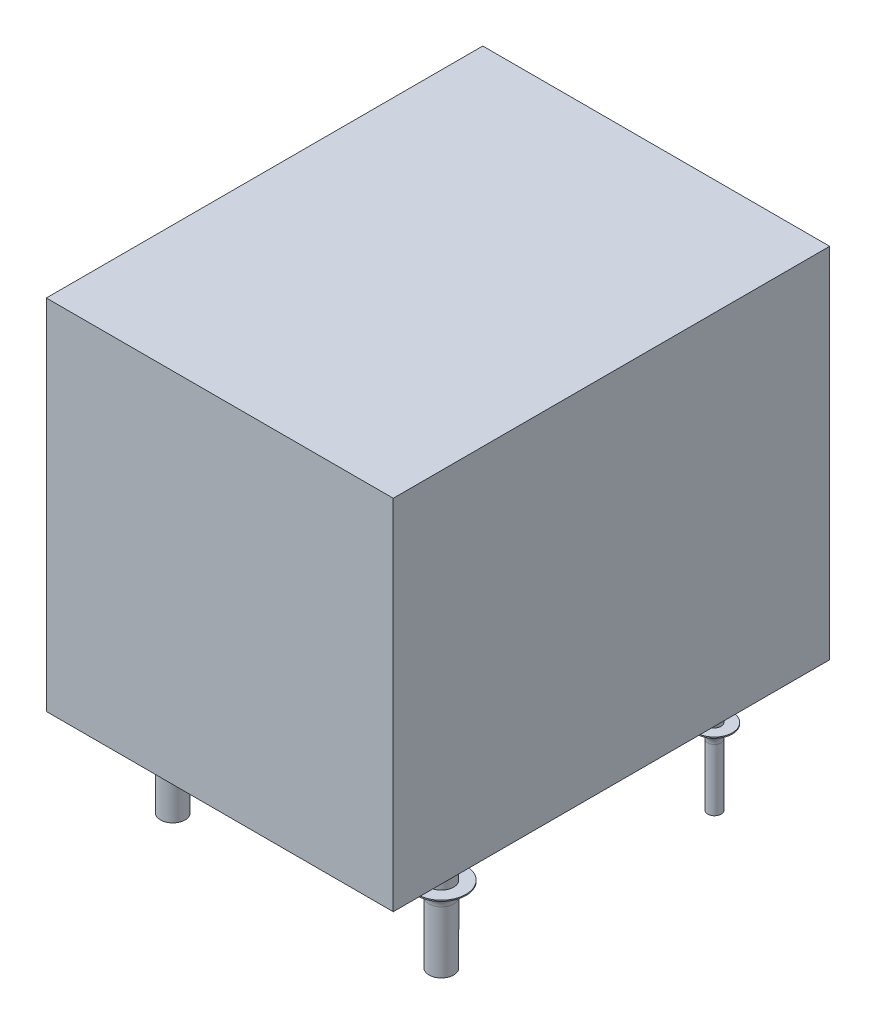
SolidWorks part; units mm, degrees
ref_plane "Plan de face" through (0, 0, 0) normal (0, 0, 1) x (1, 0, 0)
ref_plane "Plan de dessus" through (0, 0, 0) normal (0, 1, 0) x (1, 0, 0)
ref_plane "Plan de droite" through (0, 0, 0) normal (1, 0, 0) x (0, 0, -1)
sketch "Esquisse1" plane through (0, 0, 0) normal (0, 1, 0) x (1, 0, 0)
  line L1 (0, 0) -> (15.5, 0)
  line L2 (0, 0) -> (0, 19.5)
  line L3 (0, 19.5) -> (15.5, 19.5)
  line L4 (15.5, 0) -> (15.5, 19.5)
  dimension "D1" = 15.5
  dimension "D2" = 19.5
extrude "Boss.-Extru.1" add sketch "Esquisse1" along normal blind 16
sketch "Esquisse2" plane through (0, 0, 0) normal (0, -1, 0) x (1, 0, 0)
  line L0 (15.5, -19.5) -> (0, -19.5) construction
  line L1 (1.75, -3.9) -> (13.75, -3.9) construction
  line L2 (7.75, -3.9) -> (7.75, -18.1) construction
  line L3 (1.75, -3.9) -> (1.75, -16.1) construction
  line L4 (1.75, -16.1) -> (13.75, -16.1) construction
  line L5 (13.75, -3.9) -> (13.75, -16.1) construction
  circle A0 centre (1.75, -3.9) radius 0.55
  circle A1 centre (13.75, -3.9) radius 0.55
  circle A2 centre (7.75, -18.1) radius 0.55
  circle A3 centre (1.75, -16.1) radius 0.3
  circle A4 centre (13.75, -16.1) radius 0.3
  point P8 (7.75, -19.5)
  point P9 (16.4422, -7.9159)
  point P10 (-17.0348, -3.2)
  dimension "D5" = 0.6
  dimension "D6" = 1.1
  dimension "D1" = 12.2
  dimension "D2" = 12
  dimension "D3" = 2
  dimension "D4" = 1.4
extrude "Boss.-Extru.2" add sketch "Esquisse2" along normal blind 5
sketch "Esquisse4" plane through (0, 0, 0) normal (0, -1, 0) x (1, 0, 0)
  circle A0 centre (1.75, -3.9) radius 1.1
  circle A1 centre (13.75, -3.9) radius 1.1
  circle A2 centre (7.75, -18.1) radius 1.1
  circle A3 centre (1.75, -16.1) radius 0.8
  circle A4 centre (13.75, -16.1) radius 0.8
  dimension "D1" = 2.2
  dimension "D2" = 1.6
extrude "Boss.-Extru.3" add sketch "Esquisse4" along normal blind 0.05 from offset 1.6
fillet "Congé1" radius 0.6 5 edges at (1.75, -1.65, -16.4) (13.75, -1.65, -16.4) (7.75, -1.65, -18.65) (13.75, -1.65, -4.45) (1.75, -1.65, -4.45)
